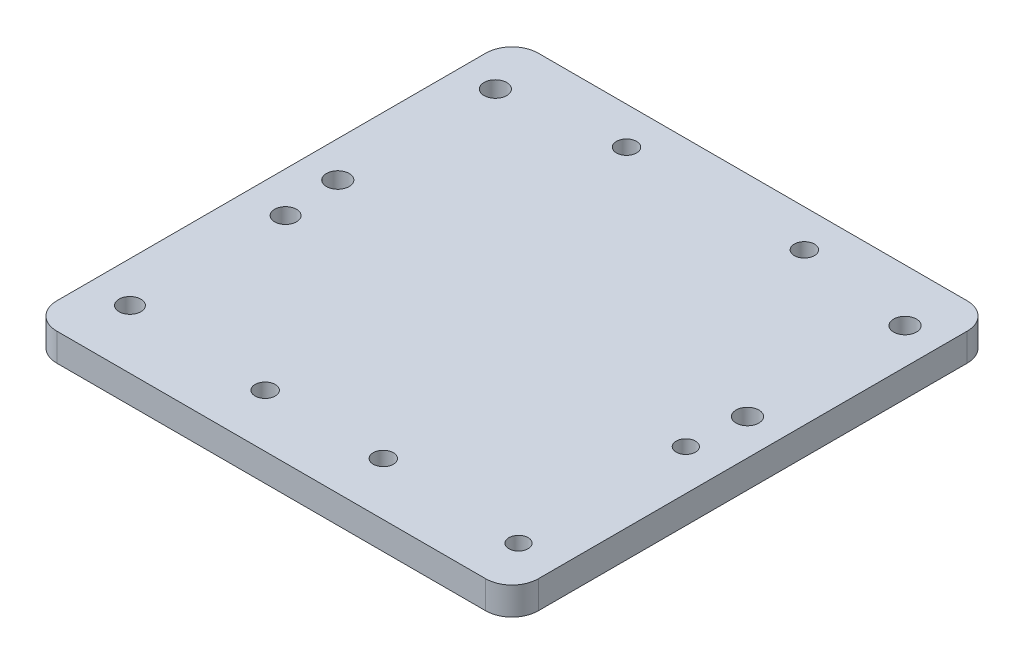
SolidWorks part; units mm, degrees
ref_plane "Front Plane" through (0, 0, 0) normal (0, 0, 1) x (1, 0, 0)
ref_plane "Top Plane" through (0, 0, 0) normal (0, 1, 0) x (1, 0, 0)
ref_plane "Right Plane" through (0, 0, 0) normal (1, 0, 0) x (0, 0, -1)
sketch "Sketch1" plane through (0, 0, 0) normal (0, 1, 0) x (1, 0, 0)
  line L1 (-27.5, 27.5) -> (27.5, 27.5)
  line L2 (-27.5, 27.5) -> (-27.5, -27.5)
  line L3 (-27.5, -27.5) -> (27.5, -27.5)
  line L4 (27.5, 27.5) -> (27.5, -27.5)
  line L5 (-27.5, 27.5) -> (27.5, -27.5) construction
  line L6 (-27.5, -27.5) -> (27.5, 27.5) construction
  point P0 (0, 0)
  dimension "D1" = 55
  dimension "D2" = 55
extrude "Boss-Extrude1" add sketch "Sketch1" along normal blind 3.175
sketch "Sketch2" plane through (0, 3.175, 0) normal (0, 1, 0) x (1, 0, 0)
  line L0 (0, 27.5) -> (0, -27.5) construction
  line L1 (27.5, 27.5) -> (-27.5, 27.5) construction
  line L2 (-27.5, -27.5) -> (27.5, -27.5) construction
  line L3 (-27.5, 27.5) -> (-27.5, -27.5) construction
  circle A0 centre (-23.4, 21.5) radius 1.3
  circle A1 centre (-23.4, 3.5) radius 1.3
  circle A2 centre (23.4, 3.5) radius 1.3
  circle A3 centre (23.4, 21.5) radius 1.3
  point P11 (-22.1, 21.5)
  point P17 (22.1, 21.5)
  dimension "D1" = 2.6
  dimension "D2" = 18
  dimension "D3" = 5.4
  dimension "D4" = 6
extrude "Cut-Extrude1" cut sketch "Sketch2" against normal up to surface (3.175 mm away) up to face at (0, 0, 0)
fillet "Fillet1" radius 3 4 edges at (-27.5, 1.5875, 27.5) (27.5, 1.5875, 27.5) (27.5, 1.5875, -27.5) (-27.5, 1.5875, -27.5)
sketch "Sketch3" plane through (0, 3.175, 0) normal (0, 1, 0) x (1, 0, 0)
  line L0 (-27.5, 0) -> (27.5, 0) construction
  line L1 (-22.865, -3) -> (22.855, -3) construction
  line L2 (-22.865, -3) -> (-22.865, -20.78) construction
  line L3 (-22.865, -20.78) -> (22.855, -22.11) construction
  line L4 (22.855, -3) -> (22.855, -22.11) construction
  line L5 (-27.5, 24.5) -> (-27.5, -24.5) construction
  line L6 (27.5, -24.5) -> (27.5, 24.5) construction
  circle A0 centre (-22.865, -3) radius 1.25
  circle A1 centre (22.855, -3) radius 1.1
  circle A2 centre (22.855, -22.11) radius 1.1
  circle A3 centre (-22.865, -20.78) radius 1.25
  dimension "D1" = 2.5
  dimension "D6" = 2.2
  dimension "D2" = 45.72
  dimension "D3" = 17.78
  dimension "D4" = 19.11
  dimension "D5" = 45.72
  dimension "D7" = 3
extrude "Cut-Extrude2" cut sketch "Sketch3" against normal up to surface (3.175 mm away) up to face at (23.4, 0, -20.2)
sketch "Sketch4" plane through (0, 3.175, 0) normal (0, 1, 0) x (1, 0, 0)
  line L0 (24.5, 27.5) -> (-24.5, 27.5) construction
  line L1 (-10.16, 23.24) -> (10.16, 23.24) construction
  line L2 (-10.16, 23.24) -> (-10.16, 8) construction
  line L3 (-10.16, 8) -> (10.16, 8) construction
  line L4 (10.16, 23.24) -> (10.16, 8) construction
  line L5 (-10.16, 23.24) -> (10.16, 8) construction
  line L6 (-10.16, 8) -> (10.16, 23.24) construction
  line L7 (0, 27.5) -> (0, -27.5) construction
  line L8 (-24.5, -27.5) -> (24.5, -27.5) construction
  circle A0 centre (-10.16, 23.24) radius 1.15
  circle A1 centre (10.16, 23.24) radius 1.15
  point P0 (0, 15.62)
  point P13 (0, 0)
  dimension "D1" = 2.3
  dimension "D2" = 20.32
  dimension "D3" = 15.24
  dimension "D4" = 8
extrude "Cut-Extrude3" cut sketch "Sketch4" against normal up to surface (3.175 mm away) up to face at (-22.865, 0, 22.03)
sketch "Sketch5" plane through (0, 3.175, 0) normal (0, 1, 0) x (1, 0, 0)
  line L0 (0, 27.5) -> (0, -27.5) construction
  line L1 (24.5, 27.5) -> (-24.5, 27.5) construction
  line L2 (-24.5, -27.5) -> (24.5, -27.5) construction
  circle A0 centre (-6.75, -21.45) radius 1.15
  circle A1 centre (6.75, -21.45) radius 1.15
  dimension "D1" = 2.3
  dimension "D2" = 6.75
  dimension "D3" = 6.05
extrude "Cut-Extrude4" cut sketch "Sketch5" against normal up to surface (3.175 mm away) up to face at (-10.16, 0, -22.09)
